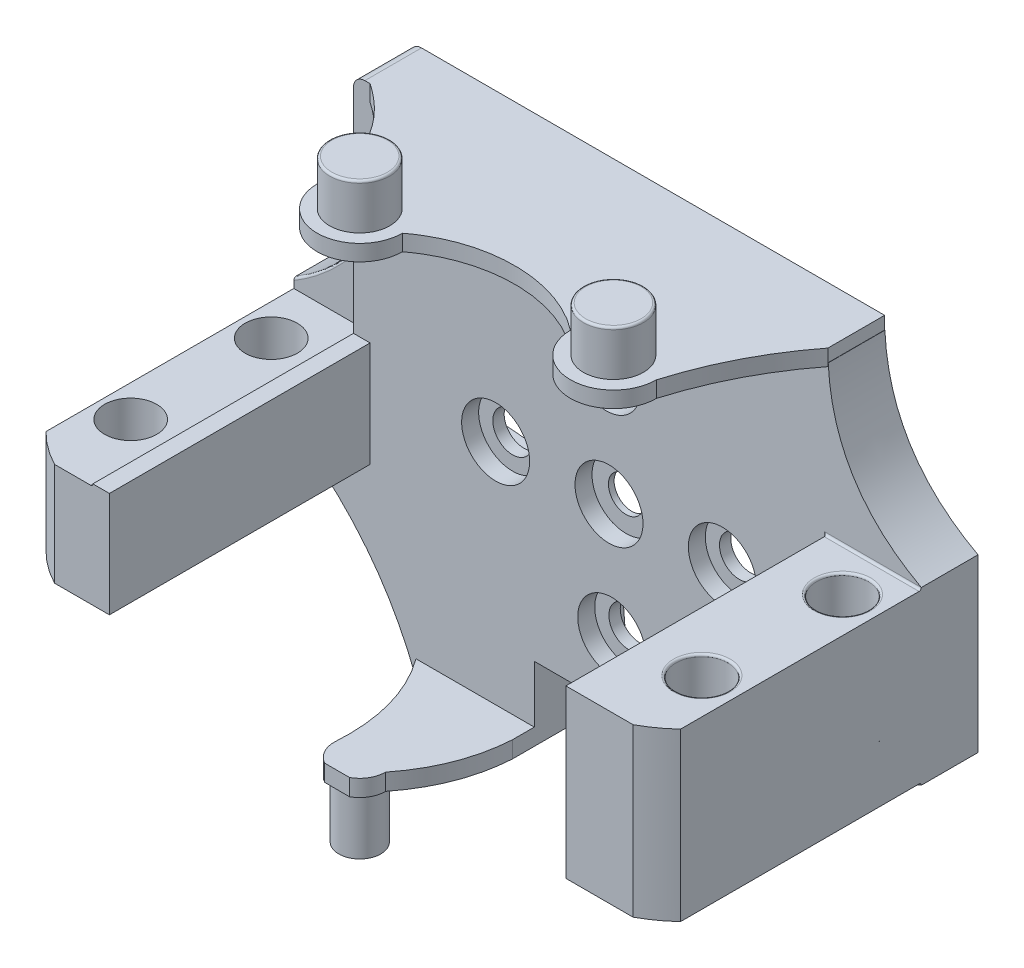
SolidWorks part; units mm, degrees
ref_plane "Front Plane" through (0, 0, 0) normal (0, 0, 1) x (1, 0, 0)
ref_plane "Top Plane" through (0, 0, 0) normal (0, 1, 0) x (1, 0, 0)
ref_plane "Right Plane" through (0, 0, 0) normal (1, 0, 0) x (0, 0, -1)
sketch "Sketch1" plane through (0, 0, 0) normal (0, 0, 1) x (1, 0, 0)
  line L201 (31.4943, -6.9757) -> (31.4943, 28.7924)
  line L202 (31.4943, 28.7924) -> (-24.3046, 28.7924)
  line L203 (-24.3046, 28.7924) -> (-24.3046, -6.9757)
  line L204 (-24.3046, -6.9757) -> (31.4943, -6.9757)
  line L1606 (1.9232, 7.8789) -> (2.0786, 7.8157)
  line L1607 (2.0505, 7.9883) -> (1.9232, 7.8789)
  line L1608 (1.8993, 8.0611) -> (2.0505, 7.9883)
  line L1609 (2.0332, 8.1623) -> (1.8993, 8.0611)
  line L1610 (1.887, 8.2445) -> (2.0332, 8.1623)
  line L1611 (2.0269, 8.337) -> (1.887, 8.2445)
  line L1612 (1.8861, 8.4282) -> (2.0269, 8.337)
  line L1613 (2.0316, 8.5118) -> (1.8861, 8.4282)
  line L1614 (1.8968, 8.6117) -> (2.0316, 8.5118)
  line L1615 (2.0473, 8.6859) -> (1.8968, 8.6117)
  line L1616 (1.919, 8.7941) -> (2.0473, 8.6859)
  line L1617 (2.0738, 8.8587) -> (1.919, 8.7941)
  line L1618 (1.9526, 8.9747) -> (2.0738, 8.8587)
  line L1619 (2.1112, 9.0295) -> (1.9526, 8.9747)
  line L1620 (1.9975, 9.1529) -> (2.1112, 9.0295)
  line L1621 (2.1592, 9.1976) -> (1.9975, 9.1529)
  line L1622 (2.0535, 9.3279) -> (2.1592, 9.1976)
  line L1623 (2.2177, 9.3624) -> (2.0535, 9.3279)
  line L1624 (2.1203, 9.4991) -> (2.2177, 9.3624)
  line L1625 (2.2864, 9.5232) -> (2.1203, 9.4991)
  line L1626 (2.1978, 9.6657) -> (2.2864, 9.5232)
  line L1627 (2.365, 9.6793) -> (2.1978, 9.6657)
  line L1628 (2.2856, 9.8271) -> (2.365, 9.6793)
  line L1629 (2.4533, 9.8302) -> (2.2856, 9.8271)
  line L1630 (2.3833, 9.9827) -> (2.4533, 9.8302)
  line L1631 (2.5509, 9.9753) -> (2.3833, 9.9827)
  line L1632 (2.4907, 10.1319) -> (2.5509, 9.9753)
  line L1633 (2.6575, 10.1139) -> (2.4907, 10.1319)
  line L1634 (2.6071, 10.274) -> (2.6575, 10.1139)
  line L1635 (2.7725, 10.2456) -> (2.6071, 10.274)
  line L1636 (2.7323, 10.4085) -> (2.7725, 10.2456)
  line L1637 (2.8956, 10.3698) -> (2.7323, 10.4085)
  line L1638 (2.8657, 10.5349) -> (2.8956, 10.3698)
  line L1639 (3.0262, 10.486) -> (2.8657, 10.5349)
  line L1640 (3.0067, 10.6527) -> (3.0262, 10.486)
  line L1641 (3.1638, 10.5938) -> (3.0067, 10.6527)
  line L1642 (3.1549, 10.7614) -> (3.1638, 10.5938)
  line L1643 (3.308, 10.6928) -> (3.1549, 10.7614)
  line L1644 (3.3096, 10.8605) -> (3.308, 10.6928)
  line L1645 (3.4581, 10.7825) -> (3.3096, 10.8605)
  line L1646 (3.4702, 10.9498) -> (3.4581, 10.7825)
  line L1647 (3.6135, 10.8625) -> (3.4702, 10.9498)
  line L1648 (3.6361, 11.0288) -> (3.6135, 10.8625)
  line L1649 (3.7736, 10.9327) -> (3.6361, 11.0288)
  line L1650 (3.8066, 11.0972) -> (3.7736, 10.9327)
  line L1651 (3.9379, 10.9927) -> (3.8066, 11.0972)
  line L1652 (3.9811, 11.1548) -> (3.9379, 10.9927)
  line L1653 (4.1055, 11.0422) -> (3.9811, 11.1548)
  line L1654 (4.1589, 11.2013) -> (4.1055, 11.0422)
  line L1655 (4.276, 11.0812) -> (4.1589, 11.2013)
  line L1656 (4.3392, 11.2366) -> (4.276, 11.0812)
  line L1657 (4.4486, 11.1093) -> (4.3392, 11.2366)
  line L1658 (4.5214, 11.2604) -> (4.4486, 11.1093)
  line L1659 (4.6225, 11.1266) -> (4.5214, 11.2604)
  line L1660 (4.7047, 11.2728) -> (4.6225, 11.1266)
  line L1661 (4.7973, 11.1329) -> (4.7047, 11.2728)
  line L1662 (4.8885, 11.2737) -> (4.7973, 11.1329)
  line L1663 (4.972, 11.1282) -> (4.8885, 11.2737)
  line L1664 (5.0719, 11.263) -> (4.972, 11.1282)
  line L1665 (5.1462, 11.1125) -> (5.0719, 11.263)
  line L1666 (5.2543, 11.2408) -> (5.1462, 11.1125)
  line L1667 (5.319, 11.086) -> (5.2543, 11.2408)
  line L1668 (5.435, 11.2072) -> (5.319, 11.086)
  line L1669 (5.4898, 11.0486) -> (5.435, 11.2072)
  line L1670 (5.6132, 11.1623) -> (5.4898, 11.0486)
  line L1671 (5.6579, 11.0006) -> (5.6132, 11.1623)
  line L1672 (5.7882, 11.1063) -> (5.6579, 11.0006)
  line L1673 (5.8227, 10.9421) -> (5.7882, 11.1063)
  line L1674 (5.9594, 11.0394) -> (5.8227, 10.9421)
  line L1675 (5.9835, 10.8734) -> (5.9594, 11.0394)
  line L1676 (6.126, 10.962) -> (5.9835, 10.8734)
  line L1677 (6.1396, 10.7948) -> (6.126, 10.962)
  line L1678 (6.2874, 10.8742) -> (6.1396, 10.7948)
  line L1679 (6.2905, 10.7064) -> (6.2874, 10.8742)
  line L1680 (6.443, 10.7764) -> (6.2905, 10.7064)
  line L1681 (6.4356, 10.6088) -> (6.443, 10.7764)
  line L1682 (6.5921, 10.6691) -> (6.4356, 10.6088)
  line L1683 (6.5742, 10.5023) -> (6.5921, 10.6691)
  line L1684 (6.7343, 10.5526) -> (6.5742, 10.5023)
  line L1685 (6.7059, 10.3873) -> (6.7343, 10.5526)
  line L1686 (6.8688, 10.4275) -> (6.7059, 10.3873)
  line L1687 (6.8301, 10.2642) -> (6.8688, 10.4275)
  line L1688 (6.9952, 10.2941) -> (6.8301, 10.2642)
  line L1689 (6.9463, 10.1336) -> (6.9952, 10.2941)
  line L1690 (7.113, 10.1531) -> (6.9463, 10.1336)
  line L1691 (7.0541, 9.9959) -> (7.113, 10.1531)
  line L1692 (7.2216, 10.0049) -> (7.0541, 9.9959)
  line L1693 (7.153, 9.8518) -> (7.2216, 10.0049)
  line L1694 (7.3208, 9.8502) -> (7.153, 9.8518)
  line L1695 (7.2427, 9.7017) -> (7.3208, 9.8502)
  line L1696 (7.4101, 9.6896) -> (7.2427, 9.7017)
  line L1697 (7.3228, 9.5463) -> (7.4101, 9.6896)
  line L1698 (7.4891, 9.5237) -> (7.3228, 9.5463)
  line L1699 (7.393, 9.3861) -> (7.4891, 9.5237)
  line L1700 (7.5575, 9.3531) -> (7.393, 9.3861)
  line L1701 (7.453, 9.2219) -> (7.5575, 9.3531)
  line L1702 (7.6151, 9.1787) -> (7.453, 9.2219)
  line L1703 (7.5025, 9.0542) -> (7.6151, 9.1787)
  line L1704 (7.6616, 9.0009) -> (7.5025, 9.0542)
  line L1705 (7.5414, 8.8838) -> (7.6616, 9.0009)
  line L1706 (7.6969, 8.8206) -> (7.5414, 8.8838)
  line L1707 (7.5696, 8.7112) -> (7.6969, 8.8206)
  line L1708 (7.7207, 8.6384) -> (7.5696, 8.7112)
  line L1709 (7.5868, 8.5372) -> (7.7207, 8.6384)
  line L1710 (7.7331, 8.455) -> (7.5868, 8.5372)
  line L1711 (7.5931, 8.3625) -> (7.7331, 8.455)
  line L1712 (7.7339, 8.2713) -> (7.5931, 8.3625)
  line L1713 (7.5884, 8.1877) -> (7.7339, 8.2713)
  line L1714 (7.7232, 8.0878) -> (7.5884, 8.1877)
  line L1715 (7.5728, 8.0136) -> (7.7232, 8.0878)
  line L1716 (7.701, 7.9054) -> (7.5728, 8.0136)
  line L1717 (7.5462, 7.8408) -> (7.701, 7.9054)
  line L1718 (7.6674, 7.7248) -> (7.5462, 7.8408)
  line L1719 (7.5089, 7.67) -> (7.6674, 7.7248)
  line L1720 (7.6226, 7.5466) -> (7.5089, 7.67)
  line L1721 (7.4609, 7.5019) -> (7.6226, 7.5466)
  line L1722 (7.5666, 7.3716) -> (7.4609, 7.5019)
  line L1723 (7.4024, 7.3371) -> (7.5666, 7.3716)
  line L1724 (7.4997, 7.2004) -> (7.4024, 7.3371)
  line L1725 (7.3337, 7.1763) -> (7.4997, 7.2004)
  line L1726 (7.4222, 7.0338) -> (7.3337, 7.1763)
  line L1727 (7.255, 7.0202) -> (7.4222, 7.0338)
  line L1728 (7.3345, 6.8724) -> (7.255, 7.0202)
  line L1729 (7.1667, 6.8693) -> (7.3345, 6.8724)
  line L1730 (7.2367, 6.7168) -> (7.1667, 6.8693)
  line L1731 (7.0691, 6.7242) -> (7.2367, 6.7168)
  line L1732 (7.1294, 6.5676) -> (7.0691, 6.7242)
  line L1733 (6.9626, 6.5856) -> (7.1294, 6.5676)
  line L1734 (7.0129, 6.4255) -> (6.9626, 6.5856)
  line L1735 (6.8476, 6.4539) -> (7.0129, 6.4255)
  line L1736 (6.8877, 6.291) -> (6.8476, 6.4539)
  line L1737 (6.7245, 6.3297) -> (6.8877, 6.291)
  line L1738 (6.7544, 6.1646) -> (6.7245, 6.3297)
  line L1739 (6.5939, 6.2135) -> (6.7544, 6.1646)
  line L1740 (6.6133, 6.0468) -> (6.5939, 6.2135)
  line L1741 (6.4562, 6.1057) -> (6.6133, 6.0468)
  line L1742 (6.4652, 5.9381) -> (6.4562, 6.1057)
  line L1743 (6.3121, 6.0067) -> (6.4652, 5.9381)
  line L1744 (6.3105, 5.839) -> (6.3121, 6.0067)
  line L1745 (6.162, 5.917) -> (6.3105, 5.839)
  line L1746 (6.1499, 5.7497) -> (6.162, 5.917)
  line L1747 (6.0066, 5.8369) -> (6.1499, 5.7497)
  line L1748 (5.984, 5.6707) -> (6.0066, 5.8369)
  line L1749 (5.8464, 5.7668) -> (5.984, 5.6707)
  line L1750 (5.8134, 5.6023) -> (5.8464, 5.7668)
  line L1751 (5.6822, 5.7068) -> (5.8134, 5.6023)
  line L1752 (5.6389, 5.5447) -> (5.6822, 5.7068)
  line L1753 (5.5145, 5.6572) -> (5.6389, 5.5447)
  line L1754 (5.4612, 5.4982) -> (5.5145, 5.6572)
  line L1755 (5.3441, 5.6183) -> (5.4612, 5.4982)
  line L1756 (5.2808, 5.4629) -> (5.3441, 5.6183)
  line L1757 (5.1715, 5.5902) -> (5.2808, 5.4629)
  line L1758 (5.0986, 5.4391) -> (5.1715, 5.5902)
  line L1759 (4.9975, 5.5729) -> (5.0986, 5.4391)
  line L1760 (4.9153, 5.4267) -> (4.9975, 5.5729)
  line L1761 (4.8228, 5.5666) -> (4.9153, 5.4267)
  line L1762 (4.7316, 5.4258) -> (4.8228, 5.5666)
  line L1763 (4.648, 5.5713) -> (4.7316, 5.4258)
  line L1764 (4.5481, 5.4365) -> (4.648, 5.5713)
  line L1765 (4.4739, 5.587) -> (4.5481, 5.4365)
  line L1766 (4.3657, 5.4587) -> (4.4739, 5.587)
  line L1767 (4.3011, 5.6135) -> (4.3657, 5.4587)
  line L1768 (4.1851, 5.4923) -> (4.3011, 5.6135)
  line L1769 (4.1302, 5.6509) -> (4.1851, 5.4923)
  line L1770 (4.0069, 5.5372) -> (4.1302, 5.6509)
  line L1771 (3.9621, 5.6989) -> (4.0069, 5.5372)
  line L1772 (3.8319, 5.5932) -> (3.9621, 5.6989)
  line L1773 (3.7974, 5.7574) -> (3.8319, 5.5932)
  line L1774 (3.6607, 5.6601) -> (3.7974, 5.7574)
  line L1775 (3.6366, 5.8261) -> (3.6607, 5.6601)
  line L1776 (3.4941, 5.7375) -> (3.6366, 5.8261)
  line L1777 (3.4804, 5.9047) -> (3.4941, 5.7375)
  line L1778 (3.3327, 5.8253) -> (3.4804, 5.9047)
  line L1779 (3.3295, 5.9931) -> (3.3327, 5.8253)
  line L1780 (3.1771, 5.9231) -> (3.3295, 5.9931)
  line L1781 (3.1845, 6.0907) -> (3.1771, 5.9231)
  line L1782 (3.0279, 6.0304) -> (3.1845, 6.0907)
  line L1783 (3.0458, 6.1972) -> (3.0279, 6.0304)
  line L1784 (2.8858, 6.1469) -> (3.0458, 6.1972)
  line L1785 (2.9142, 6.3122) -> (2.8858, 6.1469)
  line L1786 (2.7513, 6.272) -> (2.9142, 6.3122)
  line L1787 (2.79, 6.4353) -> (2.7513, 6.272)
  line L1788 (2.6249, 6.4054) -> (2.79, 6.4353)
  line L1789 (2.6737, 6.5659) -> (2.6249, 6.4054)
  line L1790 (2.5071, 6.5464) -> (2.6737, 6.5659)
  line L1791 (2.5659, 6.7036) -> (2.5071, 6.5464)
  line L1792 (2.3984, 6.6946) -> (2.5659, 6.7036)
  line L1793 (2.467, 6.8477) -> (2.3984, 6.6946)
  line L1794 (2.2992, 6.8493) -> (2.467, 6.8477)
  line L1795 (2.3773, 6.9978) -> (2.2992, 6.8493)
  line L1796 (2.21, 7.0099) -> (2.3773, 6.9978)
  line L1797 (2.2972, 7.1532) -> (2.21, 7.0099)
  line L1798 (2.131, 7.1758) -> (2.2972, 7.1532)
  line L1799 (2.2271, 7.3134) -> (2.131, 7.1758)
  line L1800 (2.0626, 7.3463) -> (2.2271, 7.3134)
  line L1801 (2.1671, 7.4776) -> (2.0626, 7.3463)
  line L1802 (2.005, 7.5208) -> (2.1671, 7.4776)
  line L1803 (2.1175, 7.6453) -> (2.005, 7.5208)
  line L1804 (1.9585, 7.6986) -> (2.1175, 7.6453)
  line L1805 (2.0786, 7.8157) -> (1.9585, 7.6986)
extrude "Boss-Extrude1" add sketch "Sketch1" against normal blind 3 and the other way blind 2
sketch "Sketch22" plane through (0, 0, -3) normal (0, 0, -1) x (-1, 0, 0)
  line L9 (-15.2125, -12.7713) -> (-15.2125, 29.8055) construction
  line L10 (5.5716, 8.1558) -> (-15.2125, 8.5171) construction
  circle A0 centre (-4.8204, 8.3365) radius 14.8896
sketch "Sketch2" plane through (0, 0, 2) normal (0, 0, 1) x (1, 0, 0)
  line L0 (24.1409, 28.4993) -> (-16.2597, 28.4993)
  line L1 (-16.2597, 28.4993) -> (-16.2597, 0.8287)
  line L3 (-16.2597, 0.8287) -> (-25.5352, 0.8287)
  line L4 (-25.5352, 0.8287) -> (-25.5352, 9.9078)
  line L5 (-25.5352, 9.9078) -> (-18.9031, 9.9078)
  line L7 (-18.9031, 9.9078) -> (-18.9031, 29.9201)
  line L9 (-18.9031, 29.9201) -> (24.1409, 29.9201)
  line L11 (24.1409, 29.9201) -> (24.1409, 28.4993)
  line L15 (31.2383, 15.5397) -> (24.0179, 15.5397)
  line L16 (31.2383, 15.5397) -> (31.2383, 0.8287)
  line L17 (31.2383, 0.8287) -> (24.0179, 0.8287)
  line L18 (24.0179, 15.5397) -> (24.0179, 0.8287)
extrude "Boss-Extrude2" add sketch "Sketch2" along normal blind 23 and the other way blind 5
sketch "Sketch3" plane through (0, 0, -3) normal (0, 0, -1) x (-1, 0, 0)
  line L0 (-31.4943, 23.1844) -> (-31.2383, 15.5397)
  line L3 (-31.2383, 15.5397) -> (-31.4943, 8.6144)
  line L4 (-31.4943, -6.9757) -> (-31.4943, 28.7924) construction
  line L5 (-31.4943, 8.6144) -> (-31.4943, 23.1844)
sketch "Sketch4" plane through (0, 0, 2) normal (0, 0, 1) x (1, 0, 0)
  line L1 (-32.0082, 9.9078) -> (-18.9031, 9.9078)
  line L2 (-32.0082, 9.9078) -> (-32.0082, 29.9201)
  line L3 (-32.0082, 29.9201) -> (-18.9031, 29.9201)
  line L4 (-18.9031, 9.9078) -> (-18.9031, 29.9201)
  line L6 (24.1409, 29.9201) -> (-18.9031, 29.9201) construction
  line L7 (-18.9031, 29.9201) -> (-18.9031, 9.9078) construction
  line L8 (-18.9031, 9.9078) -> (-25.5352, 9.9078) construction
extrude "Cut-Extrude1" cut sketch "Sketch4" against normal through all
sketch "Sketch5" plane through (0, 0, 2) normal (0, 0, 1) x (1, 0, 0)
  circle A0 centre (5.4928, 7.4278) radius 5.0977
extrude "Boss-Extrude4" add sketch "Sketch5" against normal blind 2
sketch "Sketch6" plane through (0, 0, -3) normal (0, 0, -1) x (-1, 0, 0)
  circle A2 centre (-4.8204, 8.3365) radius 1.55
extrude "Cut-Extrude2" cut sketch "Sketch6" against normal blind 12
sketch "Sketch8" plane through (0, 29.9201, 0) normal (0, 1, 0) x (1, 0, 0)
  circle A1 centre (-7.1767, -12) radius 2.65
  circle A3 centre (15.2125, -12) radius 2.65
  dimension "D1" = 5.3
  dimension "D2" = 5.3
extrude "Boss-Extrude5" add sketch "Sketch8" along normal blind 4
sketch "Sketch11" plane through (0, 0, -3) normal (0, 0, -1) x (-1, 0, 0)
  line L1 (-31.4943, 28.7924) -> (-33.2859, 28.7924)
  line L2 (-31.4943, 28.7924) -> (-31.4943, -6.9757)
  line L3 (-31.4943, -6.9757) -> (-33.2859, -6.9757)
  line L4 (-33.2859, 28.7924) -> (-33.2859, -6.9757)
extrude "Boss-Extrude6" add sketch "Sketch11" against normal up to surface (5 mm away) up to face at (6.3704, 8.3365, 2)
sketch "Sketch12" plane through (0, 0, 2) normal (0, 0, 1) x (1, 0, 0)
  line L1 (31.2383, 15.5397) -> (33.7727, 15.5397)
  line L2 (31.2383, 15.5397) -> (31.2383, 0.8287)
  line L3 (31.2383, 0.8287) -> (33.7727, 0.8287)
  line L4 (33.7727, 15.5397) -> (33.7727, 0.8287)
extrude "Boss-Extrude7" add sketch "Sketch12" along normal up to surface and the other way up to surface up to face at (27.6281, 8.1842, 25) other way up to face at (-2.2632, 12.4947, -3)
sketch "Sketch9" plane through (0, 0.8287, 0) normal (0, -1, 0) x (1, 0, 0)
  circle A0 centre (-21.1821, 18.2) radius 2.3
  circle A1 centre (-21.1821, 5.8) radius 2.3
  circle A2 centre (29.2179, 5.8) radius 2.3
  circle A3 centre (29.2179, 18.2) radius 2.3
extrude "Cut-Extrude3" cut sketch "Sketch9" against normal through all
fillet "Fillet1" radius 10 2 edges at (33.2859, 0.8287, -0.5) (33.2859, 15.5397, -0.5)
sketch "Sketch13" plane through (0, 0, 25) normal (0, 0, 1) x (1, 0, 0)
  line L0 (-18.9031, 9.9078) -> (-25.5352, 9.9078) construction
  line L1 (-25.3316, 35.5979) -> (-17.7227, 35.5979)
  line L2 (-25.3316, 35.5979) -> (-25.3316, 9.9078)
  line L3 (-25.3316, 9.9078) -> (-17.7227, 9.9078)
  line L4 (-17.7227, 35.5979) -> (-17.7227, 9.9078)
extrude "Cut-Extrude4" cut sketch "Sketch13" against normal through all
fillet "Fillet2" radius 2 1 edges at (-24.3046, 0.8287, -0.5)
sketch "Sketch14" plane through (0, 0, -3) normal (0, 0, -1) x (-1, 0, 0)
  line L0 (17.7227, 9.9078) -> (17.7227, 29.9201) construction
  line L1 (25.5352, 9.9078) -> (17.7227, 9.9078)
  line L2 (17.7227, 9.9078) -> (25.5352, 9.9078) construction
  line L3 (17.7227, 9.9078) -> (17.7227, 16.8794)
  spline S0 degree 2 poles (17.7227, 16.8794) (20.6338, 12.3118) (25.5352, 9.9078) knots 0 0 0 1 1 1
extrude "Boss-Extrude8" add sketch "Sketch14" against normal blind 4
fillet "Fillet71" radius 0.2 1 edges at (15.2125, 33.9201, 14.65)
fillet "Fillet72" radius 0.2 1 edges at (6.3704, 8.3365, 2)
fillet "Fillet74" radius 0.2 3 edges at (-17.7227, 16.8794, -1) (-17.7227, 13.3936, 1) (-17.7227, 9.9078, 13)
fillet "Fillet75" radius 0.2 3 edges at (28.8953, 0.8287, 2) (24.0179, 8.1842, 2) (28.8953, 15.5397, 2)
fillet "Fillet76" radius 0.2 3 edges at (-17.7308, 16.8816, 1.1437) (-17.813, 16.7389, 1.0328)
fillet "Fillet77" radius 0.2 1 edges at (29.2179, 0.8287, 15.9)
fillet "Fillet78" radius 0.2 1 edges at (-21.1821, 0.8287, 3.5)
fillet "Fillet79" radius 0.2 1 edges at (-21.1821, 0.8287, 15.9)
fillet "Fillet80" radius 0.2 1 edges at (26.9179, 15.5397, 5.8)
fillet "Fillet81" radius 0.2 1 edges at (29.2179, 0.8287, 3.5)
fillet "Fillet82" radius 0.2 1 edges at (26.9179, 15.5397, 18.2)
fillet "Fillet83" radius 0.2 1 edges at (-7.1767, 33.9201, 14.65)
sketch "Sketch16" plane through (0, 0.8287, 0) normal (0, -1, 0) x (1, 0, 0)
  line L0 (-26.3544, 19.3799) -> (-27.7873, 28.4979)
  line L1 (-27.7873, 28.4979) -> (-17.9227, 26.1533)
  line L2 (35.1291, 19.3799) -> (35.1291, 26.6258)
  line L3 (35.1291, 26.6258) -> (27.0543, 26.1533)
  spline S0 degree 2 poles (-17.9227, 26.1533) (-23.8559, 24.7653) (-26.3544, 19.3799) knots 0 0 0 1 1 1
  spline S1 degree 2 poles (27.0543, 26.1533) (32.6955, 24.5823) (35.1291, 19.3799) knots 0 0 0 1 1 1
extrude "Cut-Extrude6" cut sketch "Sketch16" against normal through all
sketch "Sketch17" plane through (0, 15.5397, 0) normal (0, 1, 0) x (1, 0, 0)
  line L1 (32.3797, 4.6933) -> (39.5419, 4.6933)
  line L2 (32.3797, 4.6933) -> (32.3797, -27.9347)
  line L3 (32.3797, -27.9347) -> (39.5419, -27.9347)
  line L4 (39.5419, 4.6933) -> (39.5419, -27.9347)
  line L5 (-31.1449, 5.7148) -> (-23.9872, 5.7148)
  line L6 (-31.1449, 5.7148) -> (-31.1449, -25.337)
  line L7 (-31.1449, -25.337) -> (-23.9872, -25.337)
  line L8 (-23.9872, 5.7148) -> (-23.9872, -25.337)
extrude "Cut-Extrude7" cut sketch "Sketch17" against normal through all and the other way blind 10
sketch "Sketch18" plane through (0, -6.9757, 0) normal (0, -1, 0) x (1, 0, 0)
  line L0 (-1.7704, 2) -> (-1.7704, -3)
  line L4 (-23.9872, -3) -> (32.3797, -3)
  line L5 (32.3797, -3) -> (32.3797, 2)
  line L6 (32.3797, 2) -> (-23.9872, 2)
  line L7 (32.3797, -3) -> (32.3797, 2)
  line L8 (-23.9872, -3) -> (-1.7704, -3)
  line L10 (-1.7704, 2) -> (-23.9872, 2)
  line L13 (-23.9872, 2) -> (-23.9872, -3)
  line L14 (-23.9872, 2) -> (-23.9872, -3)
  line M5 (-23.9872, -3) -> (32.3797, -3)
  line M7 (32.3797, 2) -> (-23.9872, 2)
  line M11 (-23.9872, 2) -> (-23.9872, -3)
  dimension "D1" = 0
extrude "Boss-Extrude9" add sketch "Sketch18" along normal blind 6.5 contours L0 M7 M11 M5 region at (-12.8788, -6.9757, -0.5)
sketch "Sketch19" plane through (0, 0, 2) normal (0, 0, 1) x (1, 0, 0)
  line L0 (-1.7704, -13.4757) -> (-1.7704, -6.9757) construction
  line L2 (-1.7704, -13.4757) -> (-1.7704, -12.0036)
  line L3 (-1.7704, -13.4757) -> (-12.2108, -13.4757)
  line L4 (-1.7704, -12.0036) -> (-12.2108, -12.0036)
  line L5 (-12.2108, -12.0036) -> (-12.2108, -13.4757)
extrude "Boss-Extrude10" add sketch "Sketch19" along normal blind 12
sketch "Sketch20" plane through (0, -13.4757, 0) normal (0, -1, 0) x (1, 0, 0)
  circle A1 centre (-7.1686, 12) radius 1.85
extrude "Boss-Extrude11" add sketch "Sketch20" along normal blind 5
ref_axis "Axis1" through (4.8204, 8.3365, -3) along (0, 0, -1)
sketch "Sketch23" plane through (0, 0, -3) normal (0, 0, -1) x (-1, 0, 0)
  line L0 (5.5716, 8.1558) -> (-15.2125, 8.5171) construction
  line L1 (-4.8204, -984.6635) -> (-4.8204, 15.3365) construction
  arc A0 (0.9241, 12.3365) -> (-0.8204, 14.081) centre (-4.8204, 8.3365) ccw
  arc A1 (-8.8204, 14.081) -> (-10.565, 12.3365) centre (-4.8204, 8.3365) ccw
  arc A2 (-10.565, 4.3365) -> (-8.8204, 2.5919) centre (-4.8204, 8.3365) ccw
  arc A3 (-0.8204, 2.5919) -> (0.9241, 4.3365) centre (-4.8204, 8.3365) ccw
  spline S0 degree 3 poles (-4.8204, 26.3365) (-1.2764, 26.7096) (-1.4325, 20.6709) (-0.5027, 16.5348) (-0.8204, 14.081) knots 0 0 0 0 0.519506 1 1 1 1
  spline S1 degree 3 poles (-4.8204, 26.3365) (-8.3644, 26.7096) (-8.2084, 20.6709) (-9.1382, 16.5348) (-8.8204, 14.081) knots 0 0 0 0 0.519506 1 1 1 1
  spline S2 degree 3 poles (13.1796, 8.3365) (13.5527, 11.8805) (7.514, 11.7244) (3.3779, 12.6542) (0.9241, 12.3365) knots 0 0 0 0 0.519506 1 1 1 1
  spline S3 degree 3 poles (13.1796, 8.3365) (13.5527, 4.7925) (7.514, 4.9485) (3.3779, 4.0187) (0.9241, 4.3365) knots 0 0 0 0 0.519506 1 1 1 1
  spline S4 degree 3 poles (-4.8204, -9.6635) (-1.2764, -10.0367) (-1.4325, -3.998) (-0.5027, 0.1381) (-0.8204, 2.5919) knots 0 0 0 0 0.519506 1 1 1 1
  spline S5 degree 3 poles (-4.8204, -9.6635) (-8.3644, -10.0367) (-8.2084, -3.998) (-9.1382, 0.1381) (-8.8204, 2.5919) knots 0 0 0 0 0.519506 1 1 1 1
  spline S6 degree 3 poles (-22.8204, 8.3365) (-23.1936, 4.7925) (-17.1549, 4.9485) (-13.0188, 4.0187) (-10.565, 4.3365) knots 0 0 0 0 0.519506 1 1 1 1
  spline S7 degree 3 poles (-22.8204, 8.3365) (-23.1936, 11.8805) (-17.1549, 11.7244) (-13.0188, 12.6542) (-10.565, 12.3365) knots 0 0 0 0 0.519506 1 1 1 1
  point P45 (-4.8204, 8.3365)
  dimension "D1" = 14
  dimension "D2" = 4
  dimension "D3" = 18
extrude "Cut-Extrude9" cut sketch "Sketch23" against normal blind 2.5
sketch "Sketch24" plane through (0, 0, -0.5) normal (0, 0, -1) x (-1, 0, 0)
  line L0 (-8.7502, 8.3365) -> (-1.444, 8.2095) construction
  circle A0 centre (5.1796, 8.0943) radius 1.75
  circle A1 centre (-5.0625, -1.6635) radius 1.75
  circle A2 centre (-14.8204, 8.5786) radius 1.75
  circle A3 centre (-4.5783, 18.3365) radius 1.75
  point P14 (-4.8204, 8.3365)
  dimension "D1" = 3.5
  dimension "D2" = 10
  dimension "D3" = 4
extrude "Cut-Extrude10" cut sketch "Sketch24" against normal through all
fillet "Fillet85" radius 4 1 edges at (24.1409, 29.2097, 25)
fillet "Fillet86" radius 1 1 edges at (-17.7227, 29.9201, 11)
sketch "Sketch25" plane through (0, -13.4757, 0) normal (0, -1, 0) x (1, 0, 0)
  line L0 (-12.2108, 2) -> (-13.5869, 16.8026)
  line L1 (-13.5869, 16.8026) -> (-2.2565, 16.4302)
  line L2 (-2.2565, 16.4302) -> (3.9156, 11.6367)
  line L3 (3.9156, 11.6367) -> (-1.7704, 2)
  arc A1 (-4.8901, 12) -> (-9.447, 12) centre (-7.1686, 12) ccw
  spline S0 degree 2 poles (-9.447, 12) (-9.0643, 6.3068) (-12.2108, 2) knots 0 0 0 1 1 1
  spline S1 degree 2 poles (-4.8901, 12) (-1.4396, 7.619) (-1.7704, 2) knots 0 0 0 1 1 1
  line M3 (-1.7704, -3) -> (-1.7704, 14)
  line M4 (-1.7704, 14) -> (-12.2108, 14)
  line M5 (-12.2108, 14) -> (-12.2108, 2)
extrude "Cut-Extrude11" cut sketch "Sketch25" against normal blind 10 contours S0 A1 M4 M5 | A1 L3 L2 L1 L0 M4 M3 M5 | A1 S1 M3 M4 region at (-10.9378, -13.4757, 9.2508) region at (-12.6706, -13.4757, 9.4225) region at (-3.0582, -13.4757, 11.2843)
sketch "Sketch26" plane through (0, 29.9201, 0) normal (0, 1, 0) x (1, 0, 0)
  line L2 (-16.2597, -2) -> (-16.2597, -25) construction
  line L3 (-16.2597, -2) -> (-16.2597, -25)
  line L4 (24.1409, -2) -> (24.1409, -26.7002)
  line L5 (24.1409, -26.7002) -> (-16.2597, -25)
  arc A2 (-10.9298, -12) -> (-3.4073, -12) centre (-7.1686, -12) ccw
  arc A3 (11.4228, -12) -> (19.0022, -12) centre (15.2125, -12) ccw
  spline S0 degree 2 poles (-16.2597, -2) (-10.7085, -5.7723) (-10.9298, -12) knots 0 0 0 1 1 1
  spline S1 degree 3 poles (-3.4073, -12) (0.9615, -8.6815) (7.1384, -8.7019) (11.4228, -12) knots 0 0 0 0 1 1 1 1
  spline S2 degree 2 poles (19.0022, -12) (20.6323, -6.5232) (24.1409, -2) knots 0 0 0 1 1 1
extrude "Cut-Extrude12" cut sketch "Sketch26" against normal blind 10
sketch "Sketch27" plane through (-16.2597, 0, 0) normal (1, 0, 0) x (0, 0, -1)
  line L1 (-1.2, 10.1078) -> (-25, 10.1078) construction
  line L2 (-2, 29.9201) -> (-25, 29.9201) construction
  line L3 (-2, 10.1078) -> (-25, 10.1078)
  line L4 (-2, 0.8287) -> (-2, 28.4993) construction
  line L5 (-2, 10.1078) -> (-2, 28.4993)
  line L6 (-2, 28.4993) -> (-2, 29.9201) construction
  line L7 (-2, 29.9201) -> (-25, 29.9201)
  line L8 (-2, 28.4993) -> (-2, 29.9201)
  line L9 (-25, 0.8287) -> (-25, 29.9201) construction
  line L10 (-25, 0.8287) -> (-25, 29.9201)
  line M1 (-2, 29.9201) -> (-25, 29.9201)
  line M2 (-25, 29.9201) -> (-25, 0.8287)
  line M4 (-2, 0.8287) -> (-2, 28.4993)
  line M5 (-2, 28.4993) -> (-2, 29.9201)
extrude "Cut-Extrude13" cut sketch "Sketch27" against normal blind 10 contours L3 M4 M5 M1 M2 region at (-16.2597, 20.0139, 13.5)
sketch "Sketch28" plane through (0, 0, 2) normal (0, 0, 1) x (1, 0, 0)
  line L0 (-12.2108, -13.4757) -> (-23.9872, -13.4757) construction
  line L1 (-1.7704, -6.9757) -> (32.3797, -6.9757) construction
  line L2 (-23.9872, 0.8287) -> (-31.6802, -10.2087)
  line L3 (-31.6802, -10.2087) -> (-29.0696, -16.5023)
  line L4 (-29.0696, -16.5023) -> (-12.2108, -13.4757)
  line L5 (19.927, -6.9757) -> (40.2175, -13.4757)
  line L6 (40.2175, -13.4757) -> (32.3797, 0.6287)
  line L7 (24.1409, 29.3562) -> (33.37, 31.276)
  line L8 (33.37, 31.276) -> (38.8545, 24.128)
  line L9 (38.8545, 24.128) -> (32.3797, 15.7397)
  line L10 (24.1409, 28.7924) -> (24.1409, 29.9201) construction
  spline S0 degree 2 poles (-23.9872, 0.8287) (-15.681, -4.3591) (-12.2108, -13.4757) knots 0 0 0 1 1 1
  spline S1 degree 2 poles (24.1409, 29.3562) (24.3626, 20.0598) (32.3797, 15.7397) knots 0 0 0 1 1 1
  spline S2 degree 3 poles (32.3797, 0.6287) (27.8546, -1.1544) (23.3376, -3.4156) (19.927, -6.9757) knots 0 0 0 0 1 1 1 1
extrude "Cut-Extrude14" cut sketch "Sketch28" against normal blind 10
sketch "Sketch30" plane through (0, 0, 2) normal (0, 0, 1) x (1, 0, 0)
  circle A0 centre (-5.1796, 8.0943) radius 3
  circle A1 centre (4.8204, 8.3365) radius 3
  circle A2 centre (14.8204, 8.5786) radius 3
  circle A3 centre (4.5783, 18.3365) radius 3
  circle A4 centre (5.0625, -1.6635) radius 3
  dimension "D1" = 6
  dimension "D2" = 6
  dimension "D3" = 6
  dimension "D4" = 6
  dimension "D5" = 6
extrude "Cut-Extrude15" cut sketch "Sketch30" against normal blind 1.5
